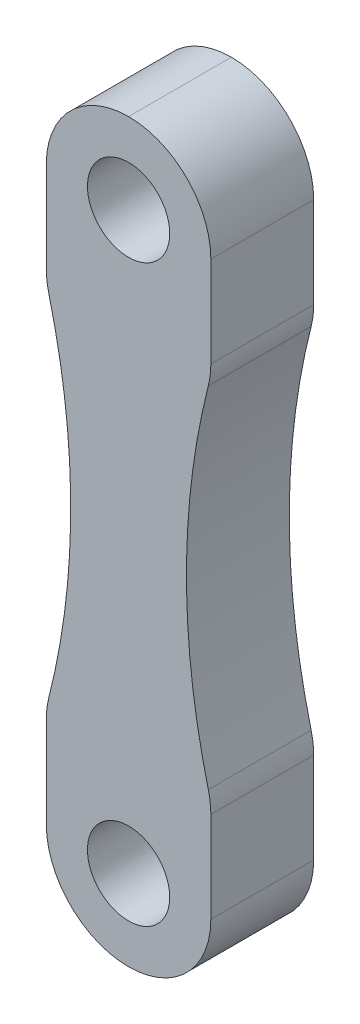
SolidWorks part; units mm, degrees
material "AISI 304"
ref_plane "Front Plane" through (0, 0, 0) normal (0, 0, 1) x (1, 0, 0)
ref_plane "Top Plane" through (0, 0, 0) normal (0, 1, 0) x (1, 0, 0)
ref_plane "Right Plane" through (0, 0, 0) normal (1, 0, 0) x (0, 0, -1)
sketch "Sketch1" plane through (0, 0, 0) normal (0, 0, 1) x (1, 0, 0)
  line L1 (-8, 35.8) -> (8, 35.8)
  line L2 (-8, 35.8) -> (-8, -35.8)
  line L3 (-8, -35.8) -> (8, -35.8)
  line L4 (8, 35.8) -> (8, -35.8)
  dimension "D1" = 8
  dimension "D2" = 8
  dimension "D3" = 35.8
  dimension "D4" = 35.8
  dimension "D5" = 71.6
  dimension "D6" = 16
extrude "Body" add sketch "Sketch1" along normal mid plane 10
sketch "Sketch2" plane through (0, 0, 5) normal (0, 0, 1) x (1, 0, 0)
  line L0 (0, -42.378) -> (0, 40.1391) construction
  circle A0 centre (0, 27.94) radius 4
  dimension "D1" = 8
  dimension "D2" = 27.94
extrude "Top Hole" cut sketch "Sketch2" against normal through all
mirror "Bottom Hole" about plane through (0, 0, 0) normal (0, 1, 0) of "Top Hole"
sketch "Sketch3" plane through (0, 0, 5) normal (0, 0, 1) x (1, 0, 0)
  line L0 (-8, 35.8) -> (-8, -35.8) construction
  line L1 (-8, 17.94) -> (-8, -17.94)
  arc A0 (-8, 17.94) -> (-8, -17.94) centre (-74.627, 0) cw
  dimension "D3" = 69
  dimension "D1" = 10
  dimension "D2" = 10
extrude "Cut-Extrude1" cut sketch "Sketch3" along normal through all and the other way through all
mirror "Mirror1" about plane through (0, 0, 0) normal (1, 0, 0) of "Cut-Extrude1"
fillet "Fillet1" radius 8 8 edges at (8, -35.8, 0) (-8, -35.8, 0) (8, 35.8, 0) (-8, 35.8, 0) (-8, -17.94, 0) (-8, 17.94, 0) (8, -17.94, 0) (8, 17.94, 0)
